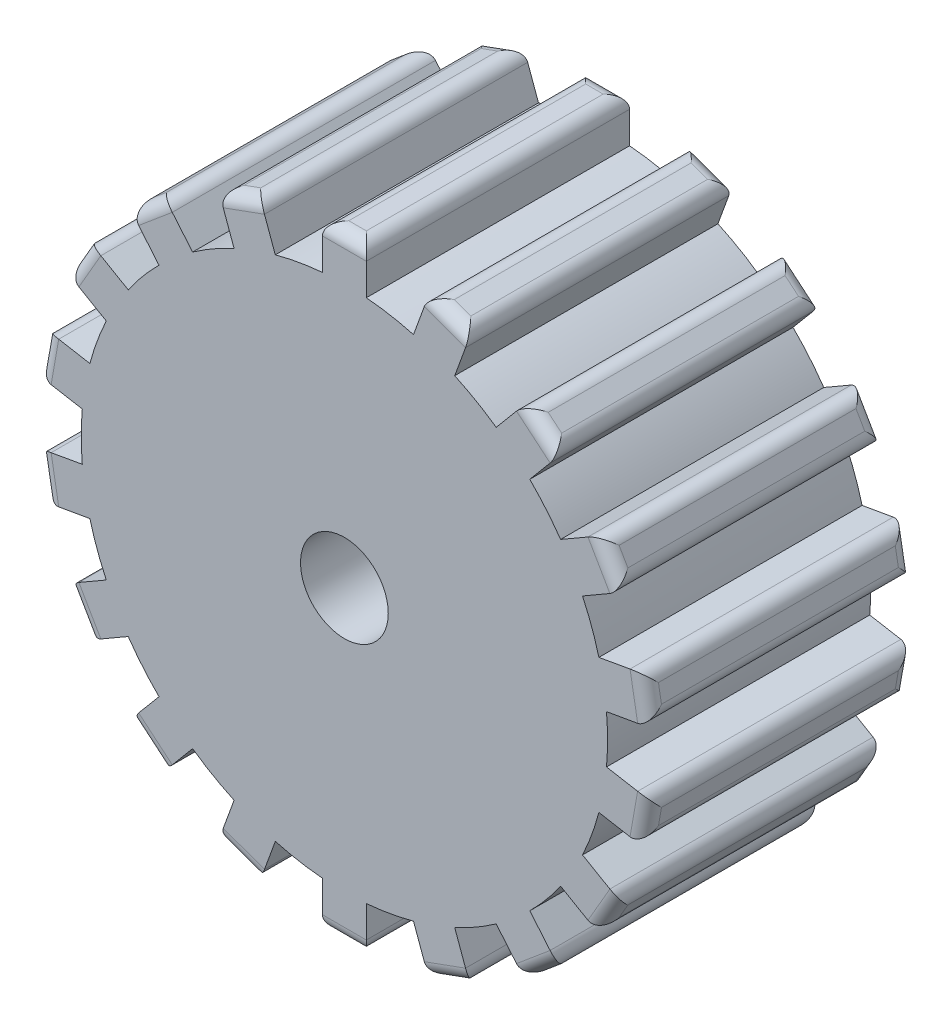
SolidWorks part; units mm, degrees
ref_plane "Front Plane" through (0, 0, 0) normal (0, 0, 1) x (1, 0, 0)
ref_plane "Top Plane" through (0, 0, 0) normal (0, 1, 0) x (1, 0, 0)
ref_plane "Right Plane" through (0, 0, 0) normal (1, 0, 0) x (0, 0, -1)
sketch "Sketch2" plane through (0, 0, 0) normal (0, 0, 1) x (1, 0, 0)
  circle A0 centre (0, 0) radius 60
extrude "Boss-Extrude1" add sketch "Sketch2" along normal blind 60
sketch "Sketch3" plane through (0, 0, 60) normal (0, 0, 1) x (1, 0, 0)
  line L0 (0, 60) -> (0, 70) construction
  line L1 (5, 70) -> (-5, 70)
  line L2 (-5, 70) -> (-5, 59.5215)
  line L3 (-5, 59.5215) -> (5, 59.5215)
  line L4 (5, 59.5215) -> (5, 70)
  circle A0 centre (0, 0) radius 60 construction
  point P9 (0, 70)
extrude "Boss-Extrude2" add sketch "Sketch3" against normal blind 60
fillet "Fillet2" radius 3 4 edges at (-5, 70, 30) (0, 70, 0) (5, 70, 30) (0, 70, 60)
pattern_circular "CirPattern1" count 18 over 360 about axis through (0, 0, 60) along (0, 0, -1) of "Fillet2", "Boss-Extrude2" reverse direction yes
sketch "Sketch4" plane through (0, 0, 60) normal (0, 0, 1) x (1, 0, 0)
  circle A0 centre (0, 0) radius 10
extrude "Cut-Extrude1" cut sketch "Sketch4" against normal blind 60
